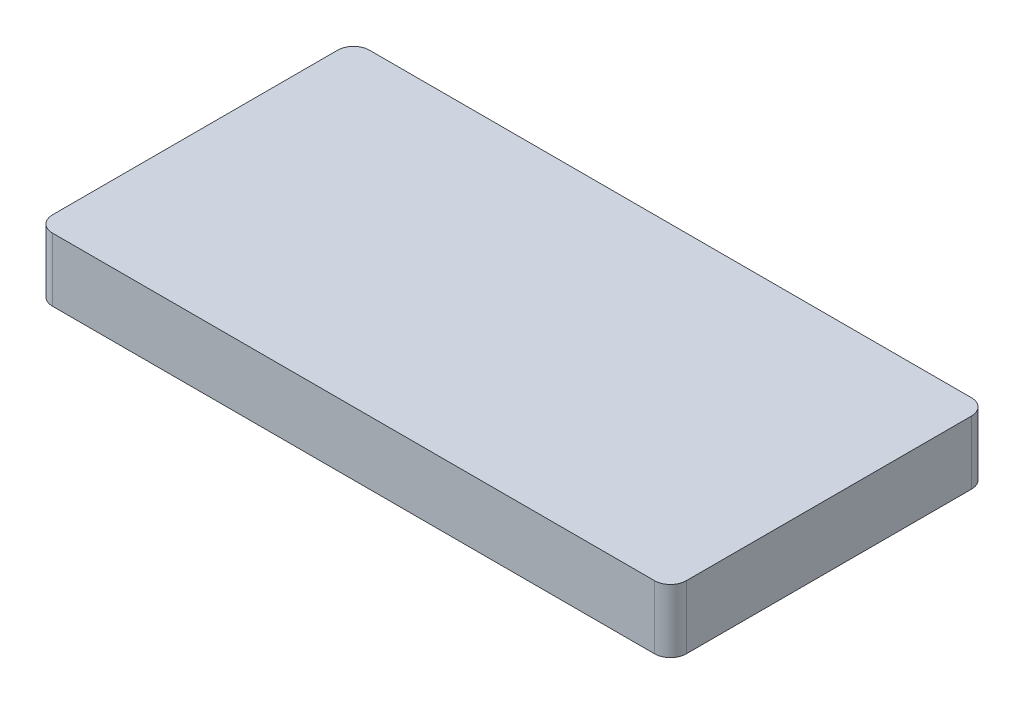
SolidWorks part; units mm, degrees
ref_plane "Front Plane" through (0, 0, 0) normal (0, 0, 1) x (1, 0, 0)
ref_plane "Top Plane" through (0, 0, 0) normal (0, 1, 0) x (1, 0, 0)
ref_plane "Right Plane" through (0, 0, 0) normal (1, 0, 0) x (0, 0, -1)
sketch "Sketch1" plane through (0, 0, 0) normal (0, 1, 0) x (1, 0, 0)
  line L0 (0, 0) -> (25.4, 0)
  line L1 (25.4, 0) -> (25.4, 12.7)
  line L2 (25.4, 12.7) -> (0, 12.7)
  line L3 (0, 12.7) -> (0, 0)
  dimension "D1" = 25.4
  dimension "D2" = 12.7
extrude "Boss-Extrude1" add sketch "Sketch1" along normal blind 2.54
fillet "Fillet1" radius 0.635 4 edges at (0, 1.27, -12.7) (25.4, 1.27, -12.7) (25.4, 1.27, 0) (0, 1.27, 0)
shell "Shell1" thickness 0.635 removed face at (12.7, 0, -6.35)
sketch "Sketch2" plane through (0, 1.905, 0) normal (0, -1, 0) x (-1, 0, 0)
  line L0 (-0.635, 6.35) -> (-24.765, 6.35) construction
  line L1 (-0.635, 12.065) -> (-0.635, 0.635) construction
  line L2 (-24.765, 0.635) -> (-24.765, 12.065) construction
  line L3 (-12.7, 0.635) -> (-12.7, 12.065) construction
  line L4 (-0.635, 0.635) -> (-24.765, 0.635) construction
  line L5 (-24.765, 12.065) -> (-0.635, 12.065) construction
  circle A0 centre (-12.7, 6.35) radius 2.54
  dimension "D1" = 5.08
extrude "Boss-Extrude2" add sketch "Sketch2" along normal up to surface (1.905 mm away) up to face at (12.7, 0, -6.35)
